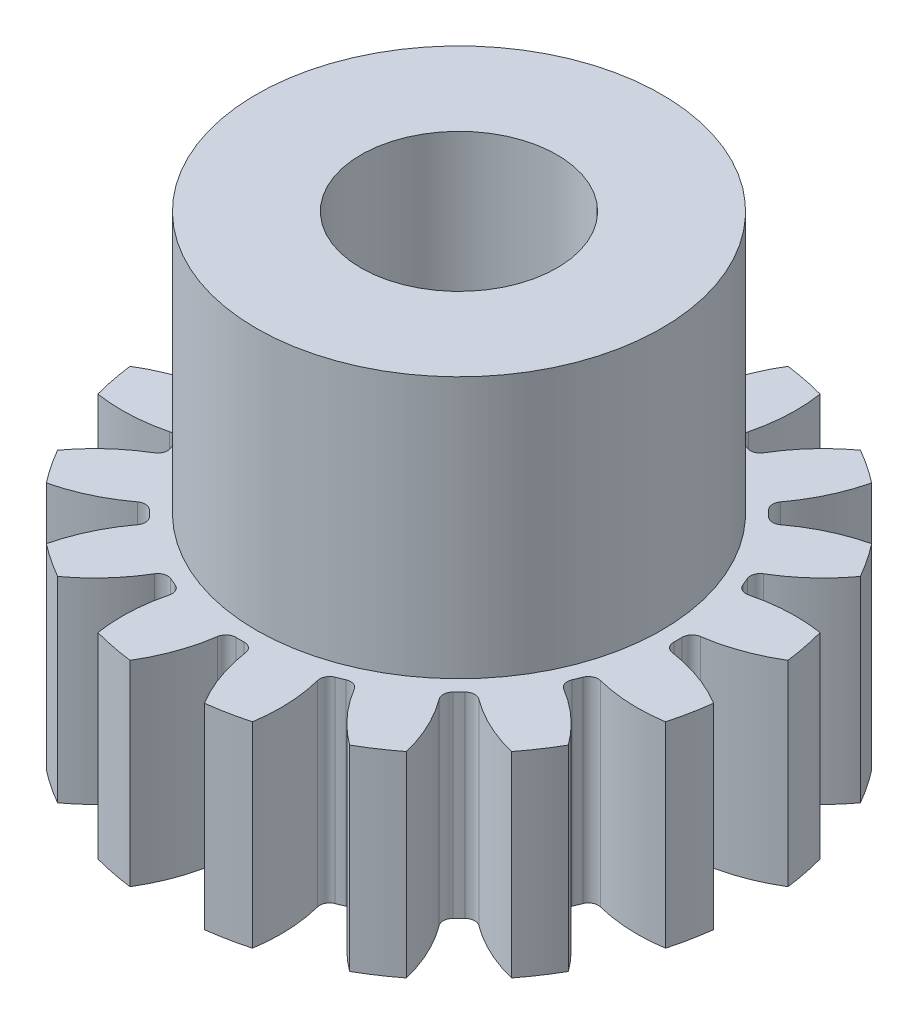
SolidWorks part; units mm, degrees
ref_plane "Front Plane" through (0, 0, 0) normal (0, 0, 1) x (1, 0, 0)
ref_plane "Top Plane" through (0, 0, 0) normal (0, 1, 0) x (1, 0, 0)
ref_plane "Right Plane" through (0, 0, 0) normal (1, 0, 0) x (0, 0, -1)
sketch "Sketch1" plane through (0, 0, 0) normal (0, 1, 0) x (1, 0, 0)
  circle A0 centre (0, 0) radius 4
  circle A1 centre (0, 0) radius 4.5
  circle A2 centre (0, 0) radius 3.3
  dimension "D1" = 8
  dimension "D2" = 9
  dimension "D3" = 1.2
extrude "Boss-Extrude1" add sketch "Sketch1" along normal mid plane 3 contours A1 A0 | A0 A2 | A2 region at (-3.8869, 0, 0) region at (-4.3727, 0, 0) region at (0, 0, 0)
sketch "Sketch3" plane through (0, 0, 0) normal (0, 1, 0) x (1, 0, 0)
  line L0 (0, 0) -> (0, 4.5) construction
  line L1 (-0.3921, 3.9807) -> (0.3921, 3.9807) construction
  line L2 (-0.2439, 3.291) -> (0, 0) construction
  line L3 (0, 2.9035) -> (-1.0108, 5.6808) construction
  line L4 (0, 0) -> (0.8779, 4.4135) construction
  line L5 (0.3921, 3.9807) -> (1.1611, 3.8278) construction
  circle A0 centre (0, 0) radius 4.5 construction
  circle A3 centre (0, 0) radius 3.3 construction
  circle A5 centre (0, 0) radius 4 construction
  circle A6 centre (0, 0) radius 4.5 construction
  arc A9 (1.6799, 5.4678) -> (-1.6799, 5.4678) centre (0, 0) ccw
  arc A10 (-1.6799, 5.4678) -> (-0.1982, 3.3441) centre (-2.8097, 3.1008) cw
  arc A11 (0.1982, 3.3441) -> (-0.1982, 3.3441) centre (0, 0) ccw
  arc A12 (1.6799, 5.4678) -> (0.1982, 3.3441) centre (2.8097, 3.1008) ccw
  point P6 (-1.8198, 5.4755)
  point P7 (-2.8097, 3.1008)
  point P9 (2.8097, 3.1008)
  point P10 (1.8198, 5.4755)
  point P11 (0.2439, 3.291)
  point P22 (0, 0)
  dimension "D2" = 20
  dimension "D3" = 11.25
extrude "Cut-Extrude1" cut sketch "Sketch3" against normal through all both and the other way through all
fillet "Fillet2" radius 0.15 2 edges at (0.1982, 0, -3.3441) (-0.1982, 0, -3.3441)
pattern_circular "CirPattern1" count 16 over 360 about axis through (0, -1.5, 0) along (0, 1, 0) of "Cut-Extrude1", "Fillet2"
sketch "Sketch4" plane through (0, 0, 0) normal (0, 1, 0) x (1, 0, 0)
  circle A0 centre (0, 0) radius 1.5
  dimension "D1" = 3
extrude "Cut-Extrude2" cut sketch "Sketch4" along normal through all both and the other way through all
sketch "Sketch5" plane through (0, 1.5, 0) normal (0, 1, 0) x (1, 0, 0)
  circle A0 centre (0, 0) radius 1.5
  circle A1 centre (0, 0) radius 3.1
  circle A2 centre (0, 0) radius 1.5 construction
  arc A4 (2.4129, 2.3239) -> (2.3239, 2.4129) centre (0, 0) ccw construction
  dimension "D1" = 0.25
extrude "Boss-Extrude2" add sketch "Sketch5" along normal blind 4
equation "\"Module\"= .5"
equation "\"Number of Teeth\"= 16"
equation "\"D1@Sketch1\"=\"Module\"* \"Number of Teeth\""
equation "\"D2@Sketch1\"=(\"Number of Teeth\" + 2) * \"Module\""
equation "\"D3@Sketch1\"=\"Module\" * if( \"Module\" => 1.25, 2.25, 2.4)"
equation "\"D3@Sketch3\"=180 / \"Number of Teeth\""
equation "\"D1@CirPattern1\"=\"Number of Teeth\""
equation "\"D1@Fillet2\"=.3 * \"Module\""
